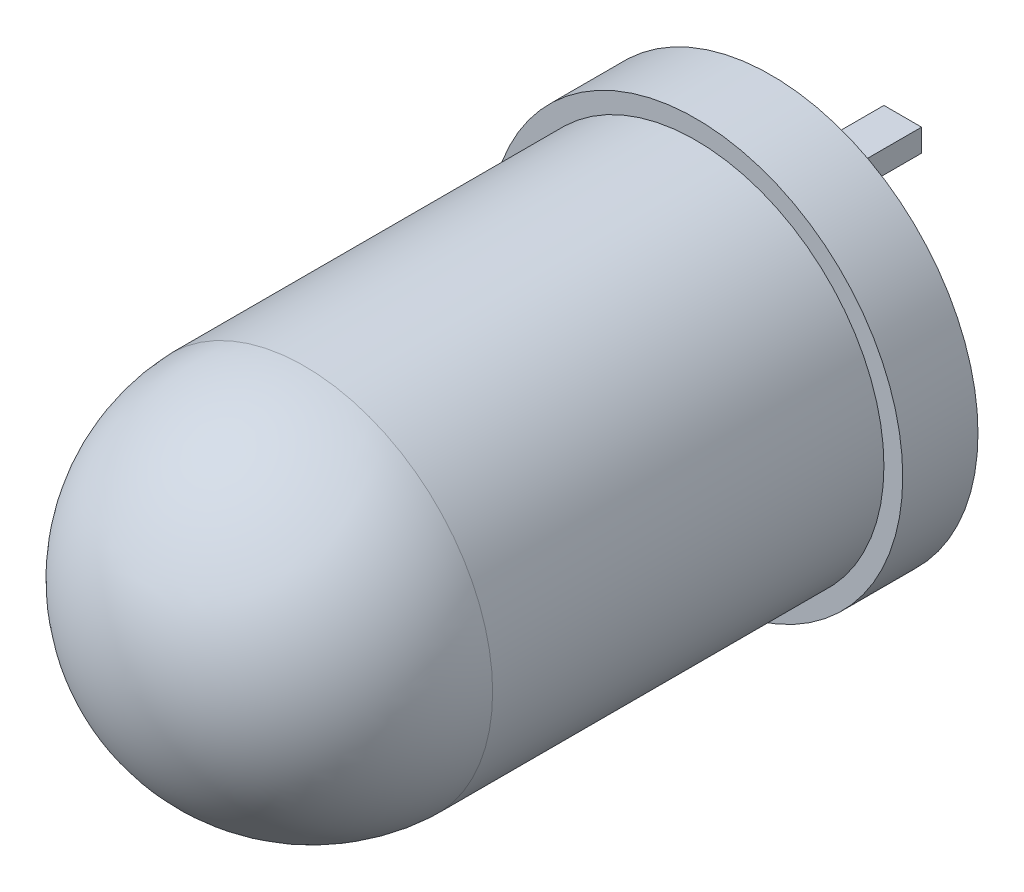
SolidWorks part; units mm, degrees
ref_plane "Front Plane" through (0, 0, 0) normal (0, 0, 1) x (1, 0, 0)
ref_plane "Top Plane" through (0, 0, 0) normal (0, 1, 0) x (1, 0, 0)
ref_plane "Right Plane" through (0, 0, 0) normal (1, 0, 0) x (0, 0, -1)
sketch "Sketch1" plane through (0, 0, 0) normal (0, 0, 1) x (1, 0, 0)
  circle A0 centre (0, 0) radius 2.5
  dimension "D1" = 5
extrude "Boss-Extrude1" add sketch "Sketch1" along normal mid plane 5.2
sketch "Sketch2" plane through (0, 0, 0) normal (0, 0, 1) x (1, 0, 0)
  circle A0 centre (0, 0) radius 2.75
  dimension "D1" = 5.5
extrude "Boss-Extrude2" add sketch "Sketch2" against normal blind 1 from surface starting at face at (2.5, 0, -2.6)
dome "Dome1" faces to dome 1 distance 2.4 reverse direction no elliptical dome no face at (2.5, 0, 2.6) parameters "D1"=2.4
sketch "Sketch3" plane through (0, 0, 0) normal (0, 0, 1) x (1, 0, 0)
  line L0 (1, 0) -> (0, 0) construction
  line L1 (1.5, 0.15) -> (1, 0.15)
  line L2 (1.5, 0.15) -> (1.5, -0.15)
  line L3 (1.5, -0.15) -> (1, -0.15)
  line L4 (1, 0.15) -> (1, -0.15)
  line L5 (-1, 0.15) -> (-1.5, 0.15)
  line L6 (-1, 0.15) -> (-1, -0.15)
  line L7 (-1, -0.15) -> (-1.5, -0.15)
  line L8 (-1.5, 0.15) -> (-1.5, -0.15)
  line L9 (0, 0) -> (-1, 0) construction
  point P8 (1, 0)
  point P9 (-1, 0)
  dimension "D1" = 0.5
  dimension "D2" = 0.3
  dimension "D3" = 2
extrude "Boss-Extrude3" add sketch "Sketch3" against normal blind 3 from surface starting at face at (2.75, 0, -3.6)
sketch "Sketch4" plane through (0, 0, 0) normal (0, 0, 1) x (1, 0, 0)
  line L1 (1, -0.15) -> (1.5, -0.15)
  line L2 (1, -0.15) -> (1, 0.15)
  line L3 (1, 0.15) -> (1.5, 0.15)
  line L4 (1.5, -0.15) -> (1.5, 0.15)
extrude "Cut-Extrude1" cut sketch "Sketch4" along normal blind 2 from surface starting at face at (1.25, 0, -6.6)
